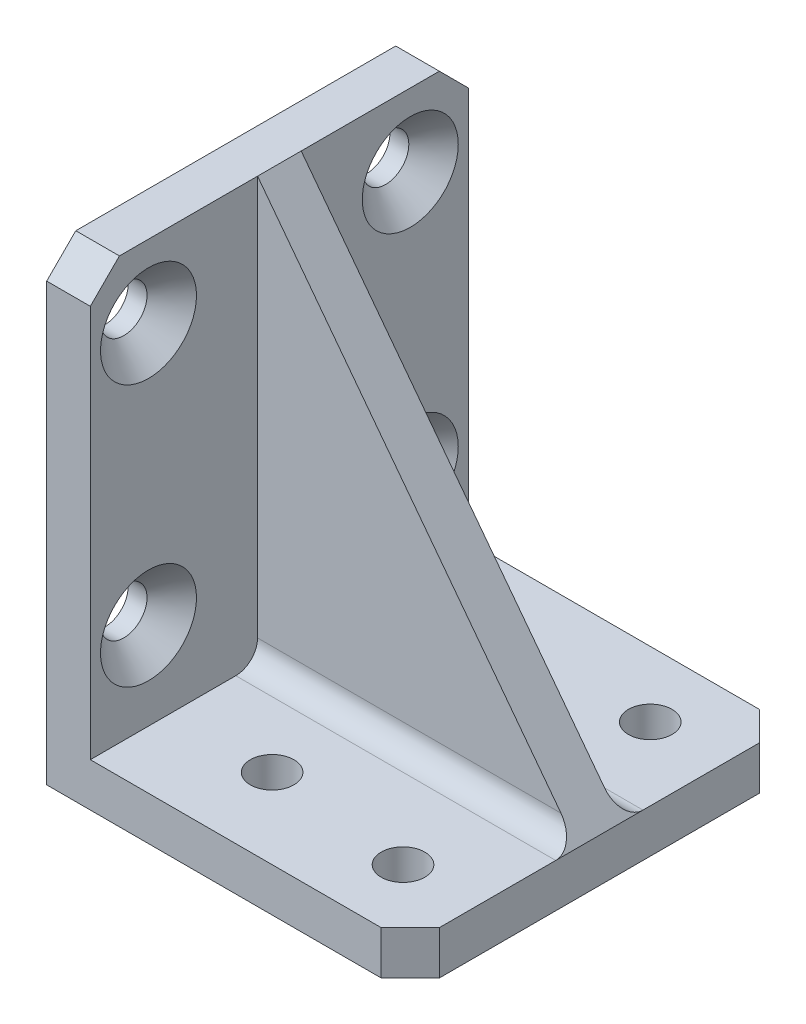
SolidWorks part; units mm, degrees
material "6061-T6 (SS)"
ref_plane "前视基准面" through (0, 0, 0) normal (0, 0, 1) x (1, 0, 0)
ref_plane "上视基准面" through (0, 0, 0) normal (0, 1, 0) x (1, 0, 0)
ref_plane "右视基准面" through (0, 0, 0) normal (1, 0, 0) x (0, 0, -1)
sketch "草图1" plane through (0, 0, 0) normal (0, 0, 1) x (1, 0, 0)
  line L0 (0, 0) -> (25, 0)
  line L1 (25, 0) -> (25, 3)
  line L2 (25, 3) -> (3, 3)
  line L3 (3, 3) -> (3, 32)
  line L4 (3, 32) -> (0, 32)
  line L5 (0, 32) -> (0, 0)
  dimension "D1" = 25
  dimension "D2" = 32
  dimension "D3" = 3
  dimension "D4" = 3
extrude "凸台-拉伸1" add sketch "草图1" along normal mid plane 26
sketch "草图4" plane through (0, 0, 0) normal (0, -1, 0) x (1, 0, 0)
  line L0 (0, 0) -> (32.0267, 0) construction
  circle A0 centre (10, -7.5) radius 1.5
  circle A1 centre (10, 7.5) radius 1.5
  circle A2 centre (20, 8.5) radius 1.5
  circle A3 centre (20, -8.5) radius 1.5
  dimension "D1" = 15
  dimension "D2" = 3
  dimension "D3" = 10
  dimension "D4" = 17
  dimension "D5" = 20
extrude "切除-拉伸1" cut sketch "草图4" against normal up to surface (3 mm away) up to face at (14, 3, 0)
sketch "草图5" plane through (3, 0, 0) normal (-1, 0, 0) x (0, 0, 1)
  line L0 (13, 32) -> (-13, 32) construction
  line L1 (0, 0) -> (0, 31.7857) construction
  circle A0 centre (-9, 27) radius 1.5
  circle A1 centre (9, 27) radius 1.5
  circle A2 centre (-9, 9) radius 1.5
  circle A3 centre (9, 9) radius 1.5
  dimension "D2" = 3
  dimension "D1" = 5
  dimension "D3" = 9
  dimension "D4" = 18
extrude "切除-拉伸2" [suppressed] cut sketch "草图5" against normal up to next
sketch "草图2" plane through (0, 0, 0) normal (0, 0, 1) x (1, 0, 0)
  line L0 (3, 32) -> (3, 3)
  line L1 (3, 3) -> (25, 3)
  line L2 (25, 3) -> (3, 32)
extrude "凸台-拉伸2" add sketch "草图2" along normal mid plane 3
chamfer "倒角1" distance 2 angle 45 4 edges at (1.5, 32, 13) (1.5, 32, -13) (25, 1.5, -13) (25, 1.5, 13)
fillet "圆角1" radius 1.5 2 edges at (14, 3, -1.5) (14, 3, 1.5)
hole_wizard "打孔尺寸(%根据)开槽半沉头木螺钉的类型1" positions "3D草图1" profile "草图6" countersink size "M3" standard "GB" end condition through all
sketch3d "3D草图1"
  point P0 (3, 9, -9)
  point P3 (3, 9, 9)
  point P6 (3, 27, 9)
  point P9 (3, 27, -9)
sketch "草图6" plane through (3, 9, -9) normal (0, 1, 0) x (0, 0, -1)
  line L0 (0, 0) -> (0, 3)
  line L1 (0, 3) -> (1.6, 3)
  line L2 (1.6, 3) -> (1.6, 1.7)
  line L3 (1.6, 1.7) -> (3.3, 0)
  line L5 (3.3, 0) -> (0, 0)
  line L6 (-1.6, 1.7) -> (-3.3, 0) construction
  line L11 (0, -6.35) -> (0, 107.95) construction
  dimension "通孔孔直径" = 3.2
  dimension "通孔孔深度" = 3
  dimension "近端锥形沉头孔直径" = 6.6
  dimension "近端锥形沉头孔角度" = 90
